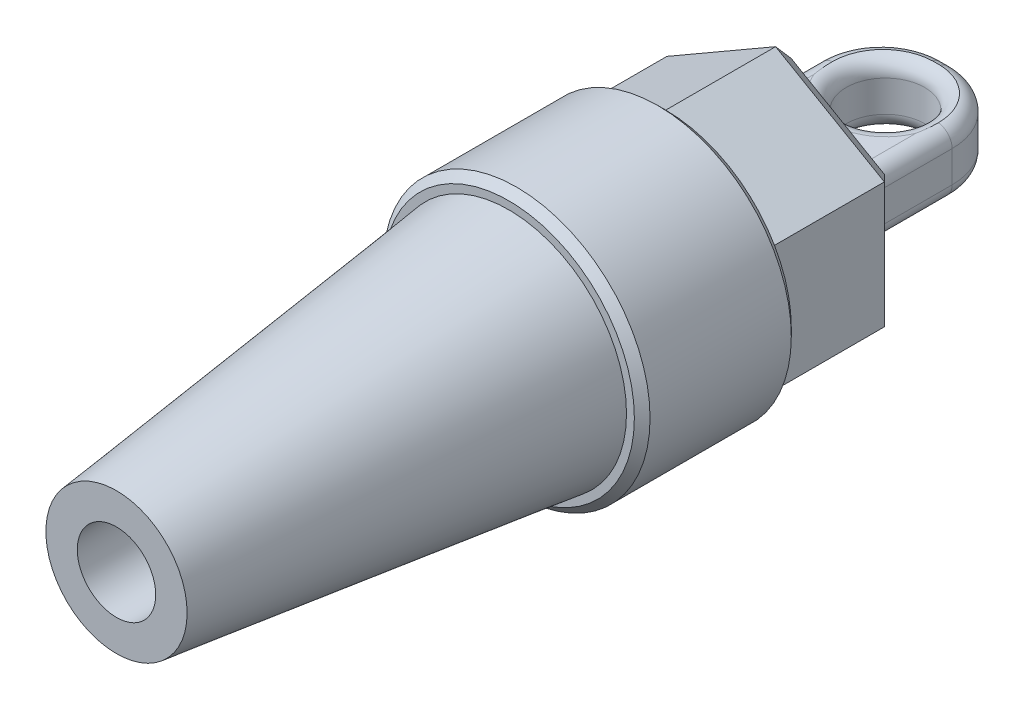
SolidWorks part; units mm, degrees
ref_plane "前视基准面" through (0, 0, 0) normal (0, 0, 1) x (1, 0, 0)
ref_plane "上视基准面" through (0, 0, 0) normal (0, 1, 0) x (1, 0, 0)
ref_plane "右视基准面" through (0, 0, 0) normal (1, 0, 0) x (0, 0, -1)
other "Configuration Table"
sketch "草图2" plane through (0, 0, 0) normal (1, 0, 0) x (0, 0, -1)
  line L0 (3.5391, 2.5) -> (3.5391, 8)
  line L1 (3.0391, 8.5) -> (-5.9609, 8.5)
  line L5 (-31.4609, 4.5) -> (-31.4609, 2.5)
  line L6 (-31.4609, 2.5) -> (3.5391, 2.5)
  line L7 (0, 0) -> (50000, 0) construction
  line L8 (-6.4609, 8) -> (-6.4609, 7.5)
  line L9 (-6.4609, 7.5) -> (-31.4609, 4.5)
  line L10 (-5.9609, 8.5) -> (-6.4609, 8)
  line L11 (3.5391, 8) -> (3.0391, 8.5)
  point P1 (3.5391, 8.5)
  point P4 (-6.4609, 8.5)
  dimension "D1" = 8.5
  dimension "D2" = 35
  dimension "D3" = 6
  dimension "D4" = 2
  dimension "D5" = 10
  dimension "D6" = 1
  dimension "D7" = 2.5
revolve "旋转1" add sketch "草图2" angle 360 about L7
sketch "草图4" plane through (0, 0, -3.5391) normal (0, 0, -1) x (-1, 0, 0)
  line L1 (0, 8) -> (-6.9282, 4)
  line L2 (-6.9282, 4) -> (-6.9282, -4)
  line L3 (-6.9282, -4) -> (0, -8)
  line L4 (0, -8) -> (6.9282, -4)
  line L5 (6.9282, -4) -> (6.9282, 4)
  line L6 (6.9282, 4) -> (0, 8)
  circle A0 centre (0, 0) radius 6.9282 construction
extrude "凸台-拉伸2" add sketch "草图4" along normal blind 8
chamfer "倒角1" distance 1 angle 45 6 edges at (-6.9282, 0, -11.5391) (-3.4641, -6, -11.5391) (3.4641, -6, -11.5391) (6.9282, 0, -11.5391) (3.4641, 6, -11.5391) (-3.4641, 6, -11.5391)
sketch "草图5" plane through (0, 0, 0) normal (0, 1, 0) x (1, 0, 0)
  line L0 (-4.25, 11.5391) -> (4.25, 11.5391)
  line L2 (-4.25, 11.5391) -> (-4.25, 17.5391)
  line L3 (-0.25, 21.5391) -> (0.25, 21.5391)
  line L4 (4.25, 11.5391) -> (4.25, 17.5391)
  arc A0 (0.25, 21.5391) -> (4.25, 17.5391) centre (0.25, 17.5391) cw
  arc A1 (-4.25, 17.5391) -> (-0.25, 21.5391) centre (-0.25, 17.5391) cw
  circle A2 centre (0, 17.5391) radius 2.5
  point P0 (0, 11.5391)
  point P2 (0, 11.5391)
  point P7 (4.25, 21.5391)
  point P13 (-4.25, 21.5391)
  dimension "D3" = 4
  dimension "D4" = 5
  dimension "D1" = 8.5
  dimension "D2" = 10
extrude "凸台-拉伸3" add sketch "草图5" along normal mid plane 4
fillet "圆角3" radius 1 16 edges at (4.25, 0, -11.5391) (-4.25, 0, -11.5391) (0, -2, -15.0391) (0, -2, -21.5391) (-3.0784, -2, -20.3675) (-4.25, -2, -14.5391) (0, -2, -11.5391) (4.25, -2, -14.5391) (3.0784, -2, -20.3675) (0, 2, -15.0391) (4.25, 2, -14.5391) (0, 2, -11.5391) (-4.25, 2, -14.5391) (-3.0784, 2, -20.3675) (0, 2, -21.5391) (3.0784, 2, -20.3675)
